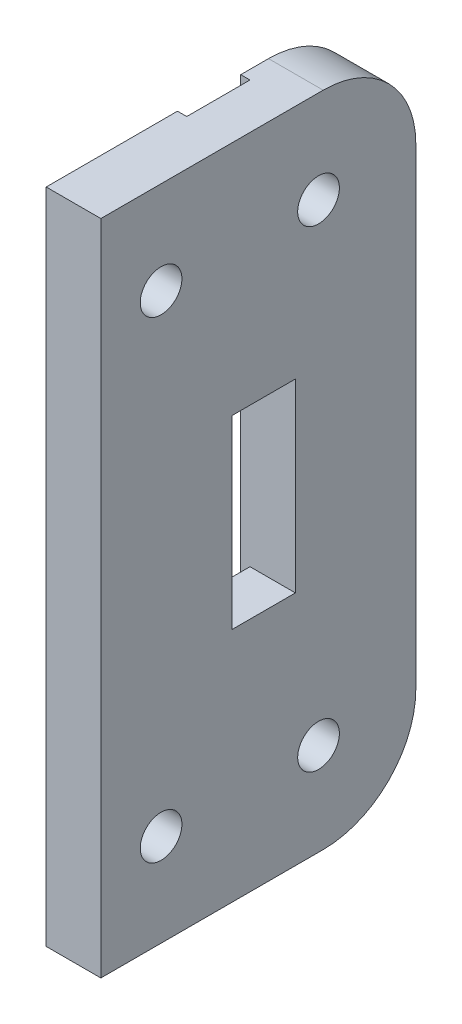
SolidWorks part; units mm, degrees
ref_plane "Front Plane" through (0, 0, 0) normal (0, 0, 1) x (1, 0, 0)
ref_plane "Top Plane" through (0, 0, 0) normal (0, 1, 0) x (1, 0, 0)
ref_plane "Right Plane" through (0, 0, 0) normal (1, 0, 0) x (0, 0, -1)
sketch "Sketch1" plane through (0, 0, 0) normal (0, 1, 0) x (1, 0, 0)
  line L0 (0, 35.8) -> (0, 1.8)
  line L4 (5.9, 1.8) -> (5.9, 35.8)
  line L5 (5.9, 35.8) -> (0, 35.8)
  line L8 (0, 1.8) -> (5.9, 1.8)
extrude "Boss-Extrude1" add sketch "Sketch1" along normal blind 71
sketch "Sketch3" plane through (0, 0, 0) normal (0, -1, 0) x (1, 0, 0)
  line L0 (0, -35.8) -> (0, -1.8) construction
  line L1 (0, -22.8) -> (1, -22.8)
  line L2 (0, -22.8) -> (0, -15.9722)
  line L3 (0, -15.9722) -> (1, -15.9722)
  line L4 (1, -22.8) -> (1, -15.9722)
  line L5 (5.9, -35.8) -> (0, -35.8) construction
  dimension "D1" = 1
  dimension "D2" = 13
  dimension "D3" = 6.8278
extrude "Cut-Extrude2" cut sketch "Sketch3" against normal up to next
fillet "Fillet1" radius 10 2 edges at (2.95, 0, -35.8) (2.95, 71, -35.8)
sketch "Sketch4" plane through (5.9, 0, 0) normal (1, 0, 0) x (0, 0, -1)
  circle A5 centre (25.3, 10) radius 2.25
  circle A6 centre (8.3, 10) radius 2.25
  circle A7 centre (8.3, 61) radius 2.25
  circle A8 centre (25.3, 61) radius 2.25
extrude "Cut-Extrude3" cut sketch "Sketch4" against normal up to next
sketch "Sketch5" plane through (5.9, 0, 0) normal (1, 0, 0) x (0, 0, -1)
  line L0 (22.8, 71) -> (22.8, 0) construction
  line L1 (22.8, 45.5) -> (15.9722, 45.5)
  line L2 (22.8, 45.5) -> (22.8, 25.5)
  line L3 (22.8, 25.5) -> (15.9722, 25.5)
  line L4 (15.9722, 45.5) -> (15.9722, 25.5)
  line L5 (15.9722, 71) -> (15.9722, 0) construction
  line L6 (35.8, 35.5) -> (-4.819, 35.5) construction
  line L7 (35.8, 61) -> (35.8, 10) construction
  point P10 (22.8, 35.5)
  dimension "D1" = 20
extrude "Cut-Extrude4" cut sketch "Sketch5" against normal up to next
sketch "Sketch6" plane through (0, 0, 0) normal (1, 0, 0) x (0, 0, -1)
  line L0 (1.8, 71) -> (1.8, 0) construction
  line L1 (15.9722, 0) -> (1.8, 0) construction
  line L2 (22.8, 0) -> (15.9722, 0) construction
  line L3 (25.8, 0) -> (22.8, 0) construction
  line L4 (35.8, 61) -> (35.8, 10) construction
  line L5 (25.8, 71) -> (22.8, 71) construction
  line L6 (22.8, 71) -> (15.9722, 71) construction
  line L7 (15.9722, 71) -> (1.8, 71) construction
  line L8 (1.8, 71) -> (1.8, 0)
  line L9 (15.9722, 0) -> (1.8, 0)
  line L10 (22.8, 0) -> (15.9722, 0)
  line L11 (25.8, 0) -> (22.8, 0)
  line L12 (35.8, 61) -> (35.8, 10)
  line L13 (25.8, 71) -> (22.8, 71)
  line L14 (22.8, 71) -> (15.9722, 71)
  line L15 (15.9722, 71) -> (1.8, 71)
  line L16 (15.9722, 71) -> (15.9722, 0) construction
  line L17 (22.8, 71) -> (22.8, 0) construction
  line L18 (22.8, 71) -> (22.8, 45.5) construction
  line L19 (15.9722, 71) -> (15.9722, 0)
  line L20 (22.8, 71) -> (22.8, 0)
  line L21 (22.8, 71) -> (22.8, 45.5)
  line L22 (22.8, 25.5) -> (15.9722, 25.5) construction
  line L23 (15.9722, 45.5) -> (22.8, 45.5) construction
  line L24 (22.8, 25.5) -> (15.9722, 25.5)
  line L25 (15.9722, 45.5) -> (22.8, 45.5)
  arc A0 (25.8, 0) -> (35.8, 10) centre (25.8, 10) ccw construction
  arc A1 (35.8, 61) -> (25.8, 71) centre (25.8, 61) ccw construction
  arc A2 (25.8, 0) -> (35.8, 10) centre (25.8, 10) ccw
  arc A3 (35.8, 61) -> (25.8, 71) centre (25.8, 61) ccw
  circle A4 centre (25.3, 10) radius 2.25 construction
  circle A5 centre (8.3, 10) radius 2.25 construction
  circle A6 centre (8.3, 61) radius 2.25 construction
  circle A7 centre (25.3, 61) radius 2.25 construction
  circle A8 centre (25.3, 10) radius 2.25
  circle A9 centre (8.3, 10) radius 2.25
  circle A10 centre (8.3, 61) radius 2.25
  circle A11 centre (25.3, 61) radius 2.25
